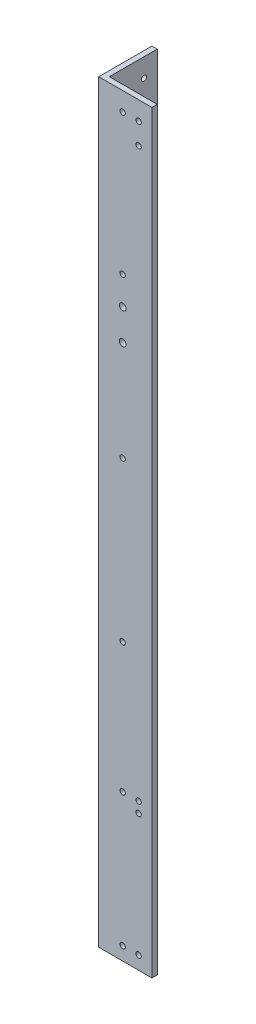
SolidWorks part; units mm, degrees
ref_plane "Front Plane" through (0, 0, 0) normal (0, 0, 1) x (1, 0, 0)
ref_plane "Top Plane" through (0, 0, 0) normal (0, 1, 0) x (1, 0, 0)
ref_plane "Right Plane" through (0, 0, 0) normal (1, 0, 0) x (0, 0, -1)
sketch "Sketch2" plane through (0, 0, 0) normal (0, 1, 0) x (1, 0, 0)
  line L0 (0, 31.75) -> (3.175, 31.75)
  line L1 (3.175, 31.75) -> (3.175, 3.175)
  line L2 (3.175, 3.175) -> (31.75, 3.175)
  line L3 (31.75, 3.175) -> (31.75, 0)
  line L4 (31.75, 0) -> (0, 0)
  line L5 (0, 0) -> (0, 31.75)
  point P9 (1.5875, 31.75)
  point P10 (31.75, 1.5875)
  dimension "D4" = 3.175
  dimension "D1" = 31.75
  dimension "D2" = 31.75
  dimension "D3" = 3.175
extrude "Boss-Extrude1" add sketch "Sketch2" along normal blind 450
sketch "FrontSideHoles-Sketch3" plane through (0, 0, 0) normal (0, 0, 1) x (1, 0, 0)
  line L0 (0, 0) -> (31.75, 0) construction
  line L1 (0, 450) -> (0, 0) construction
  circle A1 centre (23.8125, 81.1125) radius 1.5875
  circle A2 centre (14.2875, 87.4625) radius 1.5875
  circle A3 centre (23.8125, 87.4625) radius 1.5875
  circle A4 centre (14.2875, 438.8875) radius 1.5875
  circle A6 centre (23.8125, 438.8875) radius 1.5875
  circle A7 centre (23.8125, 426.1875) radius 1.5875
  circle A8 centre (14.2875, 338.1776) radius 2
  circle A9 centre (14.2875, 319.6526) radius 2
  circle A10 centre (14.2875, 260) radius 1.5875
  circle A11 centre (14.2875, 165) radius 1.5875
  circle A12 centre (14.2875, 355) radius 1.5875
  circle A13 centre (14.2875, 7.9375) radius 1.5875
  circle A14 centre (23.8125, 7.9375) radius 1.5875
  dimension "D4" = 3.175
  dimension "D15" = 4
  dimension "D8" = 11.1125
  dimension "D11" = 18.525
  dimension "D9" = 319.6526
  dimension "D6" = 165
  dimension "D10" = 95
  dimension "D13" = 95
  dimension "D12" = 7.9375
  dimension "D3" = 9.525
  dimension "D2" = 14.2875
  dimension "D5" = 6.35
  dimension "D14" = 81.1125
  dimension "D7" = 12.7
sketch "LeftSideHoles-Sketch4" plane through (0, 0, 0) normal (-1, 0, 0) x (0, 0, 1)
  line L0 (-31.75, 450) -> (0, 450) construction
  line L1 (0, 450) -> (0, 0) construction
  line L3 (-31.75, 0) -> (0, 0) construction
  circle A0 centre (-23.8125, 81.1125) radius 1.5875
  circle A1 centre (-14.2875, 81.1125) radius 1.5875
  circle A2 centre (-23.8125, 87.4625) radius 1.5875
  circle A4 centre (-23.8125, 438.8875) radius 1.5875
  circle A6 centre (-23.8125, 426.1875) radius 1.5875
  circle A7 centre (-14.2875, 426.1875) radius 1.5875
  circle A8 centre (-23.8125, 332.6026) radius 1.5875
  circle A9 centre (-14.2875, 332.6026) radius 1.5875
  circle A10 centre (-23.8125, 319.9026) radius 1.5875
  circle A11 centre (-14.2875, 319.9026) radius 1.5875
  circle A12 centre (-23.8125, 7.9375) radius 1.5875
  circle A13 centre (-14.2875, 7.9375) radius 1.5875
  circle A14 centre (-14.2875, 165) radius 1.5875
  circle A15 centre (-14.2875, 260) radius 1.5875
  circle A16 centre (-14.2875, 355) radius 1.5875
  dimension "D4" = 3.175
  dimension "D13" = 95
  dimension "D2" = 14.2875
  dimension "D5" = 6.35
  dimension "D7" = 12.7
  dimension "D3" = 81.1125
  dimension "D6" = 11.1125
  dimension "D10" = 7.9375
  dimension "D9" = 12.7
  dimension "D11" = 9.525
  dimension "D8" = 332.6026
  dimension "D12" = 165
  dimension "D14" = 95
extrude "FrontSideHoles-Cut-Extrude1" cut sketch "FrontSideHoles-Sketch3" against normal blind 3.175
extrude "LeftSideHoles-Cut-Extrude2" cut sketch "LeftSideHoles-Sketch4" against normal blind 3.175
equation "\"RailThickness\"= .125in'Spec"
equation "\"VSWidth\"= 1.25in'Spec"
equation "\"VSHeight\"= 1.25in'Spec"
equation "\"VSLength\"= 450mm"
equation "\"HoleOffsetFromEdge\"= \"RailThickness\" * 2.5"
equation "\"HoleOffsetFromSide\"= \"RailThickness\" * 3.5"
equation "\"LegHeight\"= 70mm'Space needed for PSU/Stepper/Electronics"
equation "\"VSBottomSideRailHoleY1FromBottomOfLowerRail\"= \"V1 BottomOfLowerRail\" + \"HoleOffsetFromSide\"'Equals 70.1125"
equation "\"VSSideRailHoleX1FromSide\"= \"HoleOffsetFromSide\" + \"RailThickness\""
equation "\"FasteningHoleDiameter\"= .125in"
equation "\"VSBottomSideRailHoleY2FromY1\"= \"LowerRailHeight\" - \"HoleOffsetFromSide\" - \"HoleOffsetFromEdge\"'Equals 6.35"
equation "\"VSTopSideRailHoleY1FromEdge\"= \"HoleOffsetFromEdge\" + \"RailThickness\""
equation "\"D4@FrontSideHoles-Sketch3\" = \"FasteningHoleDiameter\""
equation "\"D1@Boss-Extrude1\"=\"VSLength\""
equation "\"D4@LeftSideHoles-Sketch4\" = \"FasteningHoleDiameter\""
equation "\"D3@LeftSideHoles-Sketch4\"= \"VSBottomSideRailHoleY1FromBottomOfLowerRail\""
equation "\"D8@FrontSideHoles-Sketch3\" = \"VSTopSideRailHoleY1FromEdge\""
equation "\"D6@LeftSideHoles-Sketch4\" = \"VSTopSideRailHoleY1FromEdge\""
equation "\"VSMidSideRailHoleY1FromV8TopOfMidSideRail\"= \"V8 ToTopOfMidSideRail\" - \"HoleOffsetFromEdge\"'Equals 308.2875"
equation "\"LowerRailHeight\"= 1.00in"
equation "\"D1@Sketch2\"=\"VSHeight\""
equation "\"D2@Sketch2\"=\"VSWidth\""
equation "\"TopRailHeight\"= 1.25in"
equation "\"MidSideRailHeight\"= 1.25in"
equation "\"D10@LeftSideHoles-Sketch4\"=\"HoleOffsetFromEdge\""
equation "\"VSMidSideRailHoleY2FromY1\"= \"MidSideRailHeight\" - \"HoleOffsetFromSide\" - \"HoleOffsetFromEdge\"'Equals 12.7"
equation "\"D9@LeftSideHoles-Sketch4\"=\"VSMidSideRailHoleY2FromY1\""
equation "\"VSSideRailHoleX2FromX1\"= \"VSWidth\" - \"VSSideRailHoleX1FromSide\" - \"HoleOffsetFromEdge\""
equation "\"D11@LeftSideHoles-Sketch4\"=\"VSSideRailHoleX2FromX1\""
equation "\"VSTopSideRailHoleY2FromY1\"= \"TopRailHeight\" - \"VSTopSideRailHoleY1FromEdge\" - \"HoleOffsetFromEdge\"'Equals 12.7"
equation "\"D7@LeftSideHoles-Sketch4\"=\"VSTopSideRailHoleY2FromY1\""
equation "\"BeltTensionerInnerHeight\"= \"20TGT2PulleyWidth\" * 2 + \"1mmSpacer\" * 3"
equation "\"20TGT2PulleyWidth\"= 8.7mm'The STL of the Pulley in the diagram is a bit larger"
equation "\"1mmSpacer\"= 1mm"
equation "\"BeltTensionerHeight\"= \"BeltTensionerInnerHeight\" + \"BeltTensionerUpperLowerWallThickness\" * 2"
equation "\"BeltTensionerUpperLowerWallThickness\"= 7mm"
equation "\"D11@FrontSideHoles-Sketch3\"=\"VSBeltTensionerHoleY2FromY1\""
equation "\"VSBeltTensionerHoleY1FromBottom\"= \"V9 FromBottomGantryPulleyToBottomOfBeltTensioner\" + \"HoleOffsetFromEdge\""
equation "\"VSBeltTensionerHoleY2FromY1\"= \"BeltTensionerHeight\" - \"HoleOffsetFromEdge\" * 2"
equation "\"V1 BottomOfLowerRail\"= \"LegHeight\""
equation "\"StepperShaftLength\"= 24mm'Pulley will be attached to the end"
equation "\"ZAxisLeadScrewLength\"= 200mm"
equation "\"LM8UUHeight\"= 24mm'Spec"
equation "\"V2 ToBedAtTopOfZAxis\"= \"V1 BottomOfLowerRail\" + \"StepperShaftLength\" + \"ZAxisLeadScrewLength\" - \"LM8UUHeight\" / 2"
equation "\"HotEndToTopOfXAxisGB\"= 63.315144mm'Measured from the100.Should be 63.315144"
equation "\"TopOfGBToBottomOfLinearRail\"= \"LinearGBWidth\" / 2 + \"LinearRailWidth\" / 2"
equation "\"LinearGBWidth\"= 27mm'Spec"
equation "\"V5 ToBottomOfXAxisLinearRail\"= \"V4 ToTopOfBuildPlate/HotEndTip\" + \"HotEndToTopOfXAxisGB\" - \"TopOfGBToBottomOfLinearRail\""
equation "\"LinearRailWidth\"= 12mm'Spec"
equation "\"V6 ToBottomOfGantryPulley\"= \"V5 ToBottomOfXAxisLinearRail\" - \"DistanceFromGABTopToLowerPulley\""
equation "\"GABUpperHeight\"= 6mm"
equation "\"GABMidWallHeight\"= 28mm'Must equal 28 or changes alignment"
equation "\"GABMidShortRiserHeight\"= \"GABMidWallHeight\" / 2 - \"20TGT2PulleyWidth\"'Equals 5.3"
equation "\"GABRiserBossOffset\"= 0.8mm'Aligns Pulleys"
equation "\"DistanceFromGABTopToLowerPulley\"= \"GABUpperHeight\" + \"GABMidWallHeight\" - \"GABMidShortRiserHeight\" + \"GABRiserBossOffset\" / 2"
equation "\"V7 ToTopOfMidBackRail\"= \"V6 ToBottomOfGantryPulley\" + \"StepperShaftLength\""
equation "\"D8@LeftSideHoles-Sketch4\"= \"VSMidSideRailHoleY1FromV8TopOfMidSideRail\""
equation "\"BedToBuildPlateStandoffLength\"= 15mm"
equation "\"BuildPlateHeight\"= 8mm'Spec"
equation "\"V4 ToTopOfBuildPlate/HotEndTip\"= \"V2 ToBedAtTopOfZAxis\" + \"BedToBuildPlateStandoffLength\" + \"BuildPlateHeight\""
equation "\"D9@FrontSideHoles-Sketch3\"=\"VSBeltTensionerHoleY1FromBottom\""
equation "\"V8 ToTopOfMidSideRail\"= \"V7 ToTopOfMidBackRail\" - \"RailThickness\""
equation "\"V9 FromBottomGantryPulleyToBottomOfBeltTensioner\"= \"V6 ToBottomOfGantryPulley\" - \"BeltTensionerUpperLowerWallThickness\" - \"1mmSpacer\""
equation "\"BeltTensionerMountingHoleOffsetFromEdge\"= \"HoleOffsetFromEdge\""
equation "\"VSBeltTensionerXMountingHoleOffsetFromSide\"= \"BeltTensionerMountingHoleOffsetFromEdge\" + \"RailThickness\" * 2"
equation "\"VSEnclosureOffsets\"= ( \"VSLength\" - \"LegHeight\" ) / 4"
equation "\"D6@FrontSideHoles-Sketch3\"=\"LegHeight\" + \"VSEnclosureOffsets\""
equation "\"D10@FrontSideHoles-Sketch3\"=\"VSEnclosureOffsets\""
equation "\"D13@FrontSideHoles-Sketch3\"=\"VSEnclosureOffsets\""
equation "\"D12@FrontSideHoles-Sketch3\"=\"HoleOffsetFromEdge\""
equation "\"D13@LeftSideHoles-Sketch4\"=\"VSEnclosureOffsets\""
equation "\"D14@LeftSideHoles-Sketch4\"=\"VSEnclosureOffsets\""
equation "\"D12@LeftSideHoles-Sketch4\"=\"LegHeight\" + \"VSEnclosureOffsets\""
equation "\"D3@FrontSideHoles-Sketch3\"=\"VSSideRailHoleX2FromX1\""
equation "\"D2@FrontSideHoles-Sketch3\"=\"VSSideRailHoleX1FromSide\""
equation "\"D5@FrontSideHoles-Sketch3\"=\"VSBottomSideRailHoleY2FromY1\""
equation "\"D14@FrontSideHoles-Sketch3\"=\"VSBottomSideRailHoleY1FromBottomOfLowerRail\""
equation "\"D7@FrontSideHoles-Sketch3\"=\"VSTopSideRailHoleY2FromY1\""
equation "\"D5@LeftSideHoles-Sketch4\"=\"VSBottomSideRailHoleY2FromY1\""
equation "\"BeltTensionerMountingHoleDiameter\" = 4.0mm"
equation "\"D15@FrontSideHoles-Sketch3\"=\"BeltTensionerMountingHoleDiameter\""
